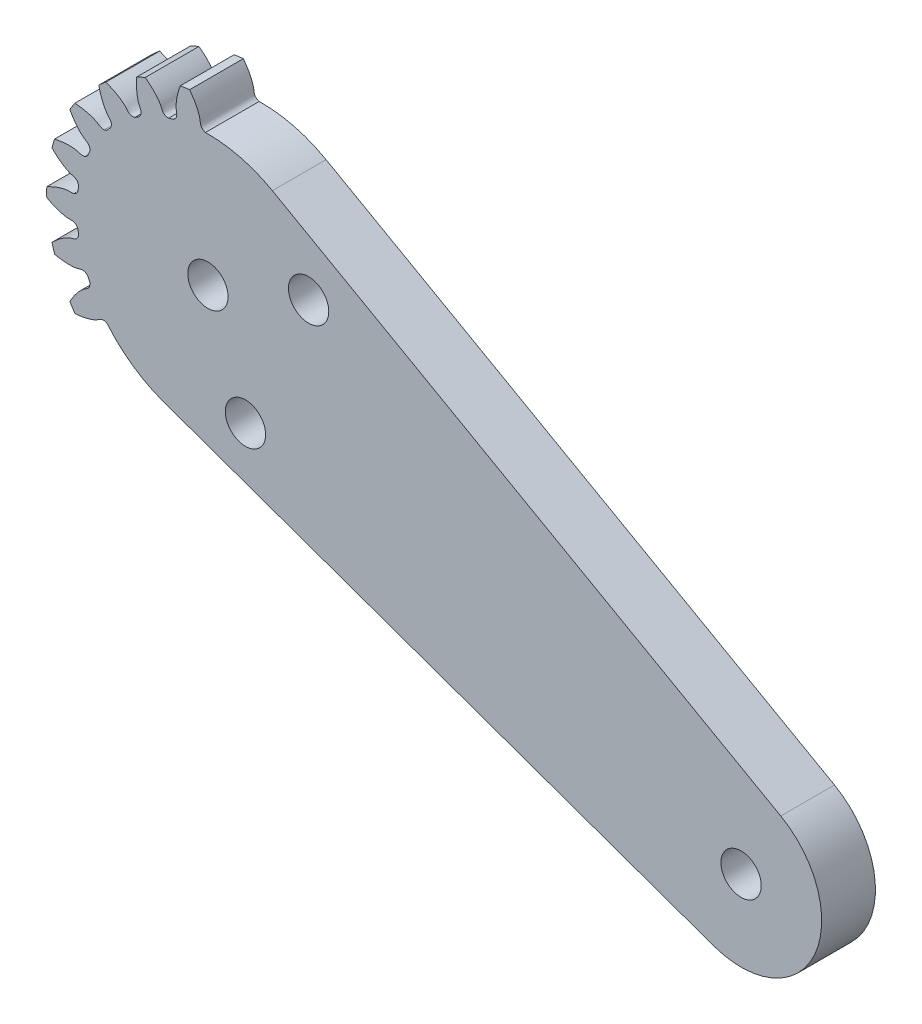
SolidWorks part; units mm, degrees
ref_plane "前视基准面" through (0, 0, 0) normal (0, 0, 1) x (1, 0, 0)
ref_plane "上视基准面" through (0, 0, 0) normal (0, 1, 0) x (1, 0, 0)
ref_plane "右视基准面" through (0, 0, 0) normal (1, 0, 0) x (0, 0, -1)
sketch "草图1" plane through (0, 0, 0) normal (0, 0, 1) x (1, 0, 0)
  circle A0 centre (0, 0) radius 12
extrude "凸台-拉伸1" add sketch "草图1" along normal blind 4
ref_axis "基准轴1" through (0, 0, -0.2) along (0, 0, 1)
sketch "草图2" plane through (0, 0, 0) normal (0, 0, 1) x (1, 0, 0)
  line L0 (0, 0) -> (0, 12) construction
  circle A0 centre (0, 0) radius 12 construction
  arc A1 (0.1857, 9.7482) -> (-0.1857, 9.7482) centre (0, 0) ccw
  arc A2 (3.0856, 13.5599) -> (-3.0856, 13.5599) centre (0, 0) ccw
  spline S0 degree 3 poles (0.1857, 9.7482) (0.5882, 9.8762) (0.5483, 10.1518) (0.5996, 10.4216) (0.606, 10.4519) (0.6139, 10.4862) (0.6235, 10.5243) (0.6349, 10.5661) (0.6484, 10.6117) (0.664, 10.661) (0.6819, 10.7139) (0.7023, 10.7703) (0.7253, 10.8301) (0.7511, 10.8933) (0.7797, 10.9597) (0.8114, 11.0293) (0.8462, 11.1021) (0.8843, 11.1778) (0.9259, 11.2563) (0.9711, 11.3377) (1.0199, 11.4217) (1.0726, 11.5082) (1.1292, 11.5972) (1.1899, 11.6884) (1.2547, 11.7818) (1.3238, 11.8773) (1.3973, 11.9746) (1.4753, 12.0737) (1.5579, 12.1744) (1.6452, 12.2766) (1.7372, 12.3802) (1.8341, 12.4849) (1.9359, 12.5906) (2.0428, 12.6972) (2.1547, 12.8044) (2.2718, 12.9123) (2.3942, 13.0205) (2.5218, 13.1289) (2.6548, 13.2373) (2.8415, 13.3834) (2.9864, 13.49) (3.0856, 13.5599) knots 0 0 0 0 0.157021 0.162531 0.168888 0.176093 0.184146 0.193046 0.202794 0.213389 0.224833 0.237123 0.250262 0.264248 0.279082 0.294763 0.311292 0.328669 0.346893 0.365965 0.385884 0.406652 0.428266 0.450729 0.474039 0.498197 0.523202 0.549055 0.575756 0.603304 0.6317 0.660944 0.691035 0.721974 0.75376 0.786395 0.819876 0.854206 0.889383 0.925408 1 1 1 1
  spline S1 degree 3 poles (-0.1857, 9.7482) (-0.5882, 9.8762) (-0.5483, 10.1518) (-0.5996, 10.4216) (-0.606, 10.4519) (-0.6139, 10.4862) (-0.6235, 10.5243) (-0.6349, 10.5661) (-0.6484, 10.6117) (-0.664, 10.661) (-0.6819, 10.7139) (-0.7023, 10.7703) (-0.7253, 10.8301) (-0.7511, 10.8933) (-0.7797, 10.9597) (-0.8114, 11.0293) (-0.8462, 11.1021) (-0.8843, 11.1778) (-0.9259, 11.2563) (-0.9711, 11.3377) (-1.0199, 11.4217) (-1.0726, 11.5082) (-1.1292, 11.5972) (-1.1899, 11.6884) (-1.2547, 11.7818) (-1.3238, 11.8773) (-1.3973, 11.9746) (-1.4753, 12.0737) (-1.5579, 12.1744) (-1.6452, 12.2766) (-1.7372, 12.3802) (-1.8341, 12.4849) (-1.9359, 12.5906) (-2.0428, 12.6972) (-2.1547, 12.8044) (-2.2718, 12.9123) (-2.3942, 13.0205) (-2.5218, 13.1289) (-2.6548, 13.2373) (-2.8415, 13.3834) (-2.9864, 13.49) (-3.0856, 13.5599) knots 0 0 0 0 0.157021 0.162531 0.168888 0.176093 0.184146 0.193046 0.202794 0.213389 0.224833 0.237123 0.250262 0.264248 0.279082 0.294763 0.311292 0.328669 0.346893 0.365965 0.385884 0.406652 0.428266 0.450729 0.474039 0.498197 0.523202 0.549055 0.575756 0.603304 0.6317 0.660944 0.691035 0.721974 0.75376 0.786395 0.819876 0.854206 0.889383 0.925408 1 1 1 1
extrude "切除-拉伸1" cut sketch "草图2" along normal through all
pattern_circular "阵列(圆周)1" count 9 every 16.364 about axis through (0, 0, -0.2) along (0, 0, 1) of "切除-拉伸1"
sketch "草图3" plane through (0, 0, 0) normal (0, 0, 1) x (1, 0, 0)
  circle A0 centre (0, 0) radius 11 construction
  dimension "Dn" = 22
sketch "草图5" plane through (0, 0, 4) normal (0, 0, 1) x (1, 0, 0)
  line L0 (-7.3851, -6.3658) -> (-10.7436, -9.2608)
  line L1 (0.9752, 14.1832) -> (0, 9.75)
  arc A0 (-7.3851, -6.3658) -> (0, 9.75) centre (0, 0) ccw
  arc A1 (-10.7436, -9.2608) -> (0.9752, 14.1832) centre (0.0145, 0.0125) ccw
extrude "切除-拉伸2" cut sketch "草图5" against normal blind 10
sketch "草图6" plane through (0, 0, 4) normal (0, 0, 1) x (1, 0, 0)
  line L0 (0, 0) -> (45481.5998, -20770.7507) construction
  line L1 (4.7976, 8.488) -> (42.6396, -12.9012)
  line L2 (37.6731, -23.7764) -> (-3.273, -9.1842)
  arc A0 (-7.4888, -6.2434) -> (-0.1857, 9.7482) centre (0, 0) ccw construction
  arc A1 (42.6396, -12.9012) -> (37.6731, -23.7764) centre (39.6872, -18.1246) cw
  arc A2 (-3.273, -9.1842) -> (4.7976, 8.488) centre (0, 0) ccw
  arc A3 (4.7976, 8.488) -> (-3.273, -9.1842) centre (0, 0) cw
  point P12 (5.3508, 8.1505)
  arc M8 (-7.4888, -6.2434) -> (-0.1857, 9.7482) centre (0, 0) ccw
  dimension "D2" = 6
  dimension "D1" = 43.63
extrude "凸台-拉伸3" add sketch "草图6" against normal up to surface (4 mm away) contours A3 L0 A1 L1 | L0 L2 A1 M8 region at (25.7493, -7.5174, 4) region at (22.5435, -14.5372, 4) up to face at (-7.0573, 3.223, 0)
sketch "草图7" plane through (0, 0, 4) normal (0, 0, 1) x (1, 0, 0)
  line L0 (0, 0) -> (10.2722, -3.9348) construction
  line L1 (10.2722, -3.9348) -> (25.8807, 36.8129) construction
  circle A0 centre (0, 0) radius 45
  dimension "D1" = 90
  dimension "D2" = 11
sketch "草图8" plane through (0, 0, 4) normal (0, 0, 1) x (1, 0, 0)
  line L0 (2.7725, -1.2661) -> (45484.3722, -20772.0168) construction
  line L1 (4.7976, 8.488) -> (42.6396, -12.9012) construction
  line L2 (37.6731, -23.7764) -> (-3.273, -9.1842) construction
  circle A1 centre (39.6872, -18.1246) radius 1.5
  circle A2 centre (2.7957, -7.4956) radius 1.5
  circle A4 centre (-7.4956, -2.7957) radius 1.5 construction
  circle A6 centre (-2.7957, 7.4956) radius 1.5 construction
  circle A8 centre (7.4956, 2.7957) radius 1.5
  circle A9 centre (0, 0) radius 1.5
  point P11 (0, 0)
  point P20 (0, 0)
  dimension "D1" = 3
  dimension "D2" = 3
  dimension "D4" = 16
  dimension "D3" = 4
extrude "切除-拉伸3" cut sketch "草图8" against normal blind 10
